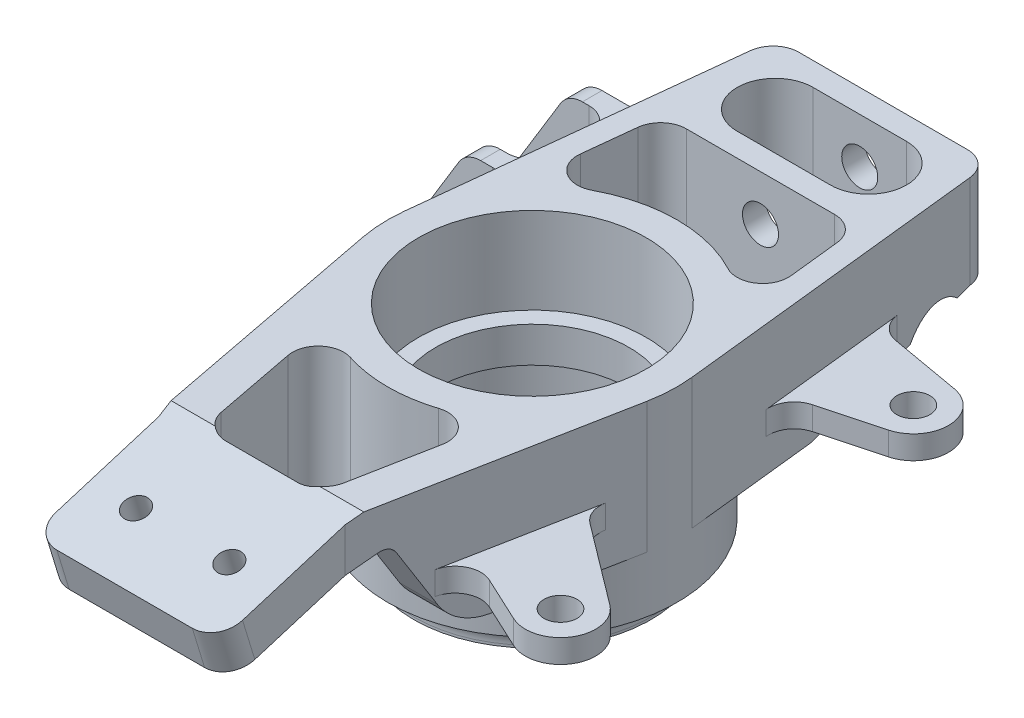
SolidWorks part; units mm, degrees
material "6061-T6 (SS)"
ref_plane "Front Plane" through (0, 0, 0) normal (0, 0, 1) x (1, 0, 0)
ref_plane "Top Plane" through (0, 0, 0) normal (0, 1, 0) x (1, 0, 0)
ref_plane "Right Plane" through (0, 0, 0) normal (1, 0, 0) x (0, 0, -1)
sketch "UBJ LBJ Geometry" plane through (0, 0, 0) normal (1, 0, 0) x (0, 0, -1)
  line L0 (0, 0) -> (0, -97.4059) construction
  line L1 (0, 0) -> (-30.7529, 0) construction
  line L2 (0, 22) -> (-45.5659, 22) construction
  line L3 (0, -10.5425) -> (-23.1063, -10.5425) construction
  line L4 (-84.7344, -51.66) -> (78.74, -22.958) construction
  line L5 (49.4563, 0) -> (49.4563, -88.2735) construction
  circle A0 centre (-84.7344, -51.66) radius 10.3251 construction
  circle A1 centre (78.74, -22.958) radius 10.3251 construction
  dimension "D7" = 20.6502
  dimension "D8" = 20.6502
  dimension "D1" = 22
  dimension "D2" = 32.5425
  dimension "D3" = 44.958
  dimension "D4" = 73.66
  dimension "D5" = 84.7344
  dimension "D6" = 78.74
  dimension "D9" = 29.2837
ref_plane "Wheel Face " through (0, 22, 0) normal (0, -1, 0) x (-1, 0, 0)
ref_plane "Upright Face" through (0, -10.5425, 0) normal (0, -1, 0) x (-1, 0, 0)
ref_plane "Tie Bracket Plane" through (0, 0, -49.4563) normal (0, 0, 1) x (1, 0, 0)
sketch "Tie Bracket Geometry" plane through (0, 0, -49.4563) normal (0, 0, 1) x (1, 0, 0)
  line L0 (0, -28.0995) -> (-60.5599, -51.7108) construction
  line L4 (0, 200000) -> (0, -200097.4059) construction
  circle A0 centre (-60.5599, -51.7108) radius 8.948 construction
  dimension "D1" = 65
  dimension "D2" = 68.7
sketch "Sketch1" plane through (0, 0, 0) normal (0, 0, 1) x (1, 0, 0)
  line L1 (-75.0953, -10.5425) -> (75.0953, -10.5425) construction
  line L2 (-39.37, -10.5425) -> (-39.37, -61.3425)
  line L3 (-39.37, -61.3425) -> (-32.258, -61.3425)
  line L4 (-32.258, -61.3425) -> (-32.258, -68.9625)
  line L5 (-32.258, -68.9625) -> (-30.9829, -68.9625)
  line L8 (-30.9829, -10.5425) -> (-30.9829, -34.0375)
  line L9 (-30.9829, -34.0375) -> (-26.289, -34.0375)
  line L10 (-26.289, -34.0375) -> (-26.289, -43.6895)
  line L11 (-26.289, -43.6895) -> (-30.9829, -43.6895)
  line L12 (-30.9829, -43.6895) -> (-30.9829, -68.9625)
  line L15 (-39.37, -10.5425) -> (-30.9829, -10.5425)
  line L17 (0, 0) -> (0, -23.5057) construction
  dimension "D1" = 9.652
  dimension "D2" = 61.9658
  dimension "D3" = 25.273
  dimension "D4" = 52.578
  dimension "D5" = 23.495
  dimension "D6" = 50.8
  dimension "D7" = 78.74
  dimension "D8" = 64.516
revolve "Bearing Housing Revolve" add sketch "Sketch1" angle 360 about L17
fillet "Bearing Housing Fillet" radius 6.985 1 edges at (0, -61.3425, 32.258)
sketch "Sketch2" plane through (0, -10.5425, 0) normal (0, -1, 0) x (-1, 0, 0)
  line L3 (39.37, -43.18) -> (39.37, 0)
  line L4 (-39.37, -43.18) -> (-39.37, 0)
  line L5 (39.37, -43.18) -> (-39.37, -43.18)
  circle A4 centre (0, 0) radius 39.37 construction
  arc A5 (39.37, 0) -> (-39.37, 0) centre (0, 0) cw
  dimension "D1" = 43.18
extrude "UBJ Prep" add sketch "Sketch2" along normal blind 35.56
sketch "Sketch3" plane through (-39.37, 0, 0) normal (-1, 0, 0) x (0, 0, 1)
  line L0 (-120.7672, 22) -> (120.7672, 22) construction
  line L1 (43.18, -10.5425) -> (72.0727, -10.5425)
  line L2 (72.0727, -10.5425) -> (110.937, -22.4245)
  line L3 (110.937, -22.4245) -> (107.5952, -33.355)
  line L4 (107.5952, -33.355) -> (68.7309, -21.473)
  line L6 (43.18, -46.1025) -> (43.18, -10.5425)
  line L7 (72.0727, -10.5425) -> (68.7309, -21.473) construction
  line L8 (104.3241, 12.415) -> (84.7344, -51.66) construction
  line L9 (55.2328, -39.1959) -> (64.6966, -23.0471)
  circle A0 centre (84.7344, -51.66) radius 12.7 construction
  arc A1 (43.18, -46.1025) -> (55.2328, -39.1959) centre (43.18, -32.1325) ccw
  arc A2 (68.7309, -21.473) -> (64.6966, -23.0471) centre (67.7098, -24.8129) ccw
  point P15 (67.617, -25.1166)
  dimension "D7" = 6.985
  dimension "D8" = 27.94
  dimension "D9" = 25.4
  dimension "D1" = 73.66
  dimension "D2" = 84.7344
  dimension "D3" = 11.43
  dimension "D4" = 40.64
  dimension "D5" = 17
  dimension "D6" = 16.51
extrude "UBJ Extrude " add sketch "Sketch3" against normal up to surface (78.74 mm away) up to face at (39.37, -28.3225, 21.59)
sketch "Sketch4" plane through (0, -0.4206, -0.1286) normal (0, -0.9563, -0.2924) x (1, 0, 0)
  line L0 (0, 112.6458) -> (0, 27.8969) construction
  line L1 (39.37, 112.6458) -> (-39.37, 112.6458) construction
  line L3 (-12.7, 96.1358) -> (12.7, 96.1358) construction
  circle A0 centre (-12.7, 96.1358) radius 3.2639
  circle A1 centre (12.7, 96.1358) radius 3.2639
  point P8 (0, 96.1358)
  dimension "D2" = 6.5278
  dimension "D1" = 25.4
extrude "Camber Block Holes" cut sketch "Sketch4" against normal up to surface (11.43 mm away) up to face at (0, -16.4835, 91.5049)
sketch "Sketch5" plane through (0, -46.1025, 0) normal (0, -1, 0) x (1, 0, 0)
  line L0 (-25.4, 107.5952) -> (-25.4, 76.3532)
  line L1 (25.4, 110.937) -> (39.37, 110.937)
  line L2 (39.37, 107.5952) -> (-39.37, 107.5952) construction
  line L4 (-25.4, 76.3532) -> (-38.6608, 7.4393)
  line L5 (25.4, 107.5952) -> (25.4, 76.3532)
  line L6 (25.4, 76.3532) -> (38.6608, 7.4393)
  line L7 (-25.4, 107.5952) -> (-25.4, 110.937)
  line L8 (39.37, 110.937) -> (-39.37, 110.937) construction
  line L9 (25.4, 107.5952) -> (25.4, 110.937)
  line L10 (-25.4, 110.937) -> (-39.37, 110.937)
  line L11 (-39.37, 110.937) -> (-39.37, 0)
  line L12 (39.37, 110.937) -> (39.37, 0)
  line L13 (-15.5718, 73.66) -> (15.5718, 73.66)
  line L14 (-15.5718, 73.66) -> (-23.6959, 31.4404)
  line L15 (15.5718, 73.66) -> (23.6959, 31.4404)
  arc A0 (-39.37, 0) -> (-38.6608, 7.4393) centre (0, 0) cw
  circle A1 centre (0, 0) radius 39.37 construction
  arc A2 (39.37, 0) -> (-39.37, 0) centre (0, 0) ccw construction
  arc A3 (39.37, 0) -> (38.6608, 7.4393) centre (0, 0) ccw
  arc A4 (-23.6959, 31.4404) -> (23.6959, 31.4404) centre (0, 0) cw
  point P31 (0, 73.66)
  dimension "D1" = 25.4
  dimension "D2" = 10.16
  dimension "D3" = 31.242
  dimension "D4" = 73.66
extrude "Weight Saving" cut sketch "Sketch5" against normal through all
fillet "Fillet2" radius 6.985 4 edges at (23.6959, -28.3225, 31.4404) (-23.6959, -28.3225, 31.4404) (15.5718, -17.0039, 73.66) (-15.5718, -17.0039, 73.66)
sketch "Sketch6" plane through (0, -10.5425, 0) normal (0, -1, 0) x (-1, 0, 0)
  line L0 (-39.37, 0) -> (-39.37, 40.64)
  line L1 (-39.37, 40.64) -> (39.37, 40.64)
  line L2 (39.37, 40.64) -> (39.37, 0)
  circle A0 centre (0, 0) radius 39.37 construction
  arc A1 (-39.37, 0) -> (39.37, 0) centre (0, 0) cw
  dimension "D1" = 40.64
extrude "LBJ Prep" add sketch "Sketch6" along normal blind 35.56
sketch "Sketch8" plane through (-39.37, 0, 0) normal (-1, 0, 0) x (0, 0, 1)
  line L0 (-40.64, -10.5425) -> (-95.4151, -10.5425)
  line L1 (-95.4151, -10.5425) -> (-95.4151, -35.9425)
  line L2 (-95.4151, -35.9425) -> (-89.0651, -35.9425)
  line L7 (-40.64, -46.1025) -> (-40.64, -10.5425)
  line L8 (-120.7672, 22) -> (120.7672, 22) construction
  line L9 (-89.0651, -35.9425) -> (-89.0651, -10.5425) construction
  line L10 (-89.0651, -35.9425) -> (-40.64, -46.1025)
  circle A0 centre (-78.74, -22.958) radius 10.3251 construction
  dimension "D3" = 20.6502
  dimension "D1" = 78.74
  dimension "D2" = 44.958
  dimension "D4" = 6.35
  dimension "D5" = 25.4
extrude "LBJ Area " add sketch "Sketch8" against normal up to surface (78.74 mm away) up to face at (39.37, -28.3225, -20.32)
sketch "Sketch7" plane through (0, -46.1025, 0) normal (0, -1, 0) x (1, 0, 0)
  line L0 (-12.7, -78.74) -> (12.7, -78.74) construction
  line L1 (0, -200000) -> (0, 200045.5659) construction
  line L2 (-12.7, -68.4149) -> (12.7, -68.4149)
  line L3 (-12.7, -89.0651) -> (12.7, -89.0651)
  line L4 (-29.21, -95.4151) -> (-39.1385, -4.2631)
  line L5 (39.37, -95.4151) -> (-39.37, -95.4151) construction
  line L6 (29.21, -95.4151) -> (39.1385, -4.2631)
  line L7 (-29.21, -95.4151) -> (-39.37, -95.4151)
  line L8 (-39.37, -95.4151) -> (-39.37, 0)
  line L9 (29.21, -95.4151) -> (39.37, -95.4151)
  line L10 (39.37, -95.4151) -> (39.37, 0)
  line L13 (-26.455, -62.0649) -> (26.455, -62.0649)
  line L14 (26.455, -62.0649) -> (30.5043, -24.8895)
  line L15 (-26.455, -62.0649) -> (-30.5043, -24.8895)
  arc A0 (-12.7, -68.4149) -> (-12.7, -89.0651) centre (-12.7, -78.74) ccw
  arc A1 (12.7, -89.0651) -> (12.7, -68.4149) centre (12.7, -78.74) ccw
  circle A2 centre (0, 0) radius 39.37 construction
  arc A3 (-39.37, 0) -> (39.37, 0) centre (0, 0) ccw construction
  arc A4 (39.37, 0) -> (39.1385, -4.2631) centre (0, 0) cw
  arc A5 (-39.37, 0) -> (-39.1385, -4.2631) centre (0, 0) ccw
  arc A6 (-30.5043, -24.8895) -> (30.5043, -24.8895) centre (0, 0) ccw
  point P4 (0, -78.74)
  point P28 (0, -62.0649)
  dimension "D1" = 78.74
  dimension "D2" = 20.6502
  dimension "D3" = 25.4
  dimension "D4" = 10.16
  dimension "D5" = 6.35
  dimension "D6" = 6.35
extrude "LBJ Taper And Slot" cut sketch "Sketch7" against normal up to surface (35.56 mm away) up to face at (0, -10.5425, 30.9829)
fillet "Fillet3" radius 6.985 4 edges at (26.455, -26.0749, -62.0649) (-26.455, -26.0749, -62.0649) (30.5043, -28.3225, -24.8895) (-30.5043, -28.3225, -24.8895)
extrude "LBJ Holes 3/8 Close Fit Hole" cut sketch "Sketch9" against normal up to surface (33.3502 mm away) up to face at (0, -26.0749, -62.0649)
sketch "Sketch9" plane through (0, 0, -95.4151) normal (0, 0, -1) x (-1, 0, 0)
  circle A0 centre (0, -22.958) radius 4.9022
  dimension "D2" = 9.8044
  dimension "D1" = 22.958
ref_plane "Brake Mounting Plane" through (0, -30.7025, 0) normal (0, 1, 0) x (1, 0, 0)
sketch "Sketch10" plane through (0, -30.7025, 0) normal (0, 1, 0) x (1, 0, 0)
  line L0 (87.9814, 0) -> (161.3053, 0) construction
  line L1 (0, 72.9505) -> (0, 47.1638) construction
  line L2 (55.6514, 48) -> (55.6514, -48) construction
  line L3 (58.1309, 38.7464) -> (36.0276, 32.8239)
  line L4 (39.1385, 4.2631) -> (29.21, 95.4151) construction
  line L5 (36.0276, 32.8239) -> (32.8776, 61.7434)
  line L6 (32.8776, 61.7434) -> (57.3149, 57.4345)
  line L7 (61.4168, -40.3491) -> (36.0119, -21.2051)
  line L8 (26.2237, -72.0727) -> (38.6608, -7.4393) construction
  line L9 (36.0119, -21.2051) -> (31.031, -47.0897)
  line L10 (31.031, -47.0897) -> (51.6027, -56.6824)
  circle A0 centre (55.6514, 48) radius 4.5
  circle A1 centre (55.6514, -48) radius 4.5
  arc A2 (51.6027, -56.6824) -> (61.4168, -40.3491) centre (55.6514, -48) ccw
  arc A3 (58.1309, 38.7464) -> (57.3149, 57.4345) centre (55.6514, 48) ccw
  point P7 (55.6514, 0)
  dimension "D2" = 9
  dimension "D3" = 5.08
  dimension "D4" = 5.08
  dimension "D1" = 96
  dimension "D5" = 55.6514
  dimension "D6" = 80
  dimension "D7" = 75
  dimension "D8" = 53
  dimension "D9" = 65
extrude "Brake Mounts" add sketch "Sketch10" against normal blind 6.35
fillet "Fillet4" radius 6.985 4 edges at (36.0119, -33.8775, 21.2051) (31.031, -33.8775, 47.0897) (36.0276, -33.8775, -32.8239) (32.8776, -33.8775, -61.7434)
sketch "Sketch17" plane through (0, -37.0525, 0) normal (0, -1, 0) x (1, 0, 0)
  line L1 (36.8349, 16.928) -> (29.3384, 55.8861) construction
  line L3 (32.3099, -66.9555) -> (36.6761, -26.8705) construction
  line L6 (57.3149, -57.4345) -> (38.0409, -60.833) construction
  line L12 (61.4168, 40.3491) -> (39.4904, 23.8263) construction
  circle A0 centre (40.1682, 38.2515) radius 4.7625
  circle A1 centre (41.7635, -47.6031) radius 4.7625
  dimension "D1" = 9.525
  dimension "D2" = 9.525
  dimension "D3" = 2.54
  dimension "D4" = 2.54
  dimension "D5" = 7.62
  dimension "D6" = 6.35
extrude "rotor Cut " [suppressed] cut sketch "Sketch17" against normal up to surface (6.35 mm away) up to plane "Brake Mounting Plane"
sketch "Sketch16" plane through (0, -46.1025, 0) normal (0, 1, 0) x (1, 0, 0)
  line L0 (-38.6345, 8.89) -> (-55.7371, 8.89)
  line L1 (-38.6608, -7.4393) -> (-26.2237, -72.0727) construction
  line L2 (-55.7371, 8.89) -> (-55.7371, -8.89)
  line L3 (-55.7371, -8.89) -> (-38.3816, -8.89)
  line L5 (-29.21, 95.4151) -> (-39.1385, 4.2631) construction
  line L6 (-38.6345, 8.89) -> (-38.3816, -8.89)
  circle A0 centre (-46.609, 0) radius 5.9531
  point P8 (-55.7371, 0)
  dimension "D1" = 3.175
  dimension "D3" = 11.9062
  dimension "D2" = 46.609
  dimension "D4" = 17.78
extrude "Speed Sensor Mount" add sketch "Sketch16" along normal blind 5.08
fillet "Speed Sensor Fillet" radius 6.985 4 edges at (-55.7371, -43.5625, 8.89) (-55.7371, -43.5625, -8.89) (-38.3816, -43.5625, 8.89) (-38.6345, -43.5625, -8.89)
thread "15/32-32" pitch 0.9071 method cut profile "Thread Profile1" start angle 0, offset 1, length 10, pitch 0.7937, diameter 11.9062
ref_plane "Plane1" through (-40.6559, -45.1025, 0) normal (0, 0, 1) x (1, 0, 0)
sketch "Thread Profile1" plane through (-40.6559, -45.1025, 0) normal (0, 0, 1) x (1, 0, 0)
  line L0 (0, 0) -> (0, 0.9071) construction
  line L1 (0, 0) -> (0.491, 0.2835)
  line L2 (0.491, 0.2835) -> (0.491, 0.3969)
  line L3 (0.491, 0.3969) -> (0, 0.6804)
  line L4 (0.491, 0.3402) -> (0, 0.3402) construction
  line L11 (0, 0) -> (0, 0.6804)
  point P2 (0, 0)
  dimension "Pitch" = 0.9071
  dimension "Profile_Angle" = 60
  dimension "Profile_Land" = 0.1134
  dimension "Profile_Height" = 0.491
sketch "Sketch12" plane through (0, 0, -49.4563) normal (0, 0, 1) x (1, 0, 0)
  line L0 (0, 3.2946) -> (0, -38.5659) construction
  line L1 (-90.5661, 0) -> (-38.2005, 0) construction
  line L2 (-68.726, -10.5425) -> (-68.726, -51.7108)
  line L3 (-52.3938, -10.5425) -> (-52.3938, -51.7108)
  line L4 (-68.726, -10.5425) -> (-52.3938, -10.5425)
  line L6 (-75.0953, -10.5425) -> (75.0953, -10.5425) construction
  circle A0 centre (-60.5599, -51.7108) radius 3.2639
  arc A1 (-68.726, -51.7108) -> (-52.3938, -51.7108) centre (-60.5599, -51.7108) ccw
  dimension "D1" = 6.5278
  dimension "D2" = 4.9022
extrude "Initial Toe Bracket" add sketch "Sketch12" along normal blind 16.51 and the other way blind 16.51 separate body
sketch "Sketch13" plane through (-52.3938, 0, 0) normal (1, 0, 0) x (0, 0, -1)
  line L0 (32.9463, -16.8925) -> (65.9663, -16.8925)
  line L1 (65.9663, -51.7108) -> (65.9663, -10.5425) construction
  line L2 (65.9663, -16.8925) -> (65.9663, -38.4825)
  line L3 (32.9463, -16.8925) -> (32.9463, -38.4825)
  line L4 (200000, -10.5425) -> (-200023.1063, -10.5425) construction
  line L5 (32.9463, -38.4825) -> (65.9663, -38.4825)
  line L6 (32.9463, -51.7108) -> (32.9463, -10.5425) construction
  dimension "D1" = 6.35
  dimension "D2" = 21.59
extrude "Toe Bracket Connection to Upright" add sketch "Sketch13" along normal up to surface (19.9762 mm away) up to face at (-34.7109, -33.4025, -44.9123)
sketch "Sketch14" plane through (0, 0, -65.9663) normal (0, 0, -1) x (-1, 0, 0)
  line L0 (52.3938, -16.8925) -> (68.726, -16.8925)
  line L1 (68.726, -10.5425) -> (68.726, -51.7108) construction
  line L2 (68.726, -16.8925) -> (68.726, -10.5425)
  line L3 (68.726, -10.5425) -> (52.3938, -10.5425)
  line L4 (52.3938, -10.5425) -> (52.3938, -16.8925)
extrude "Excess Toe Bracket Cut" cut sketch "Sketch14" against normal up to surface (33.02 mm away) up to face at (-52.382, -30.4278, -32.9463)
sketch "Sketch19" plane through (0, 0, -32.9463) normal (0, 0, 1) x (1, 0, 0)
  line L0 (-53.5754, -55.9418) -> (-42.9993, -38.4825)
  line L1 (-42.9993, -38.4825) -> (-52.3938, -38.4825)
  line L2 (-52.3938, -38.4825) -> (-53.5754, -55.9418)
  line L3 (-36.0143, -38.4825) -> (-52.3938, -38.4825) construction
  line L4 (-36.0143, -16.8925) -> (-36.0143, -38.4825) construction
  arc A0 (-68.726, -51.7108) -> (-52.3938, -51.7108) centre (-60.5599, -51.7108) ccw construction
  dimension "D1" = 6.985
extrude "Adding To Toe" add sketch "Sketch19" against normal up to surface (33.02 mm away) up to face at (-51.1792, -37.0563, -65.9663)
sketch "Sketch20" plane through (0, 0, -32.9463) normal (0, 0, 1) x (1, 0, 0)
  line L0 (-50.946, -16.8925) -> (-68.726, -16.8925)
  line L1 (-36.0143, -16.8925) -> (-68.726, -16.8925) construction
  line L2 (-68.726, -16.8925) -> (-68.726, -46.1025)
  line L3 (-68.726, -16.8925) -> (-68.726, -51.7108) construction
  line L4 (-68.726, -46.1025) -> (-50.946, -16.8925)
  dimension "D1" = 17.78
  dimension "D2" = 29.21
extrude "Cut-Extrude1" cut sketch "Sketch20" against normal up to surface (33.02 mm away) up to face at (-50.0779, -37.3587, -65.9663)
sketch "Sketch15" plane through (-68.726, 0, 0) normal (-1, 0, 0) x (0, 0, 1)
  line L0 (-60.6323, -16.8925) -> (-38.2803, -16.8925)
  line L1 (-38.2803, -16.8925) -> (-38.2803, -59.8769)
  line L2 (-65.9663, -59.8769) -> (-32.9463, -59.8769) construction
  line L3 (-38.2803, -59.8769) -> (-60.6323, -59.8769)
  line L4 (-60.6323, -59.8769) -> (-60.6323, -16.8925)
  line L6 (-49.4563, -25.7825) -> (-49.4563, -39.109) construction
  line L8 (-32.9463, -16.8925) -> (-65.9663, -16.8925) construction
  point P9 (-49.4563, -16.8925)
  point P11 (-49.4563, -16.8925)
  dimension "D1" = 22.352
extrude "Toe Bracket Slot" cut sketch "Sketch15" against normal blind 30.48
fillet "Toe Bracket Fillet" radius 6.985 2 edges at (-32.4176, -27.6875, -65.9663) (-36.0143, -27.6875, -32.9463)
fillet "Fillet7" radius 6.985 4 edges at (-68.726, -46.1025, -35.6133) (-68.726, -46.1025, -63.2993) (-50.946, -16.8925, -63.2993) (-50.946, -16.8925, -35.6133)
fillet "Inside Toe Fillet" radius 6.985 2 edges at (-38.246, -27.6875, -38.2803) (-38.246, -27.6875, -60.6323)
fillet "Outside Fillets" radius 6.985 4 edges at (-25.4, -27.8897, 109.2661) (25.4, -27.8897, 109.2661) (29.21, -23.2425, -95.4151) (-29.21, -23.2425, -95.4151)
sketch "Angle Reference" plane through (0, 0, -95.4151) normal (0, 0, -1) x (-1, 0, 0)
  line L0 (0, -22.958) -> (32.5253, -73.0426) construction
  line L1 (0, 0) -> (0, -88.2735) construction
  line L2 (0, -22.958) -> (69.6053, -82.0294) construction
  dimension "D1" = 33
  dimension "D2" = 16.68
ref_plane "Plane2" through (0, -22.958, -78.74) normal (-0.7624, -0.6471, 0) x (0, 0, 1)
sketch "Sketch22" plane through (0, -22.958, -78.74) normal (-0.7624, -0.6471, 0) x (0, 0, 1)
  line L0 (0, 1.0566) -> (0, -4.2774) construction
  line L3 (10.3251, 1.0566) -> (10.3251, -4.2774)
  line L4 (-10.3251, 1.0566) -> (-10.3251, -4.2774)
  arc A2 (10.3251, 1.0566) -> (-10.3251, 1.0566) centre (0, 1.0566) ccw
  arc A3 (-10.3251, -4.2774) -> (10.3251, -4.2774) centre (0, -4.2774) ccw
  point P2 (0, -1.6104)
  point P8 (-3.05, -1.3536)
  point P9 (0, 1.9943)
  dimension "D1" = 20.6502
  dimension "D2" = 1.0566
  dimension "D3" = 5.334
extrude "Angle Slot Cut" cut sketch "Sketch22" along normal through all
mirror "Mirror1" about plane through (0, 0, 0) normal (1, 0, 0) of "Angle Slot Cut"
equation "\"Wheel_Offset\"= 22mm"
equation "\"HUB_to_UBJ_Lat\"= 2.9in"
equation "\"Hub_to_UBJ_Vert\"= 3.336in"
equation "\"Hub_to_LBJ_Lat\"= 1.77in"
equation "\"Hub_to_LBJ_Vert\"= 3.1in"
equation "\"Wheel_face_to_Upright_back\"= 1.2812in'This is the distance between the whee face to the upright back."
equation "\"UBJ_Angle\"= 17deg"
equation "\"D2@UBJ LBJ Geometry\" = \"Wheel_face_to_Upright_back\""
equation "\"D3@UBJ LBJ Geometry\" = \"Hub_to_LBJ_Lat\""
equation "\"D4@UBJ LBJ Geometry\" = \"HUB_to_UBJ_Lat\""
equation "\"D5@UBJ LBJ Geometry\" = \"Hub_to_UBJ_Vert\""
equation "\"D6@UBJ LBJ Geometry\" = \"Hub_to_LBJ_Vert\""
equation "\"D1@Sketch3\"=\"HUB_to_UBJ_Lat\""
equation "\"D2@Sketch3\"=\"Hub_to_UBJ_Vert\""
equation "\"D1@Sketch8\"=\"Hub_to_LBJ_Vert\""
equation "\"D2@Sketch8\"=\"Hub_to_LBJ_Lat\""
equation "\"Hub_Tie_Bracket_Vert\"= 2in'(Not Given) Ask Sus and Controls later"
equation "\"Tie_Beta\"= 21.3deg'From FE11 Master "
equation "\"Toe_Arm\"= 65mm'From FE11 Master (Assume Dist start at KPI)"
equation "\"D1@Sketch7\"=\"Hub_to_LBJ_Vert\""
equation "\"D1@Sketch9\"=\"Hub_to_LBJ_Lat\"-\"Wheel_Offset\""
equation "\"D1@Tie Bracket Geometry\" = \"Toe_Arm\""
equation "\"D2@Tie Bracket Geometry\" = 90 - \"Tie_Beta\""
equation "\"oranizeBlock\"= 0"
equation "\"BrakeAngle\"= 65deg"
equation "\"D5@Sketch3\"=\"UBJ_Angle\""
equation "\"D1@Sketch7\"=\"Hub_to_LBJ_Lat\""
